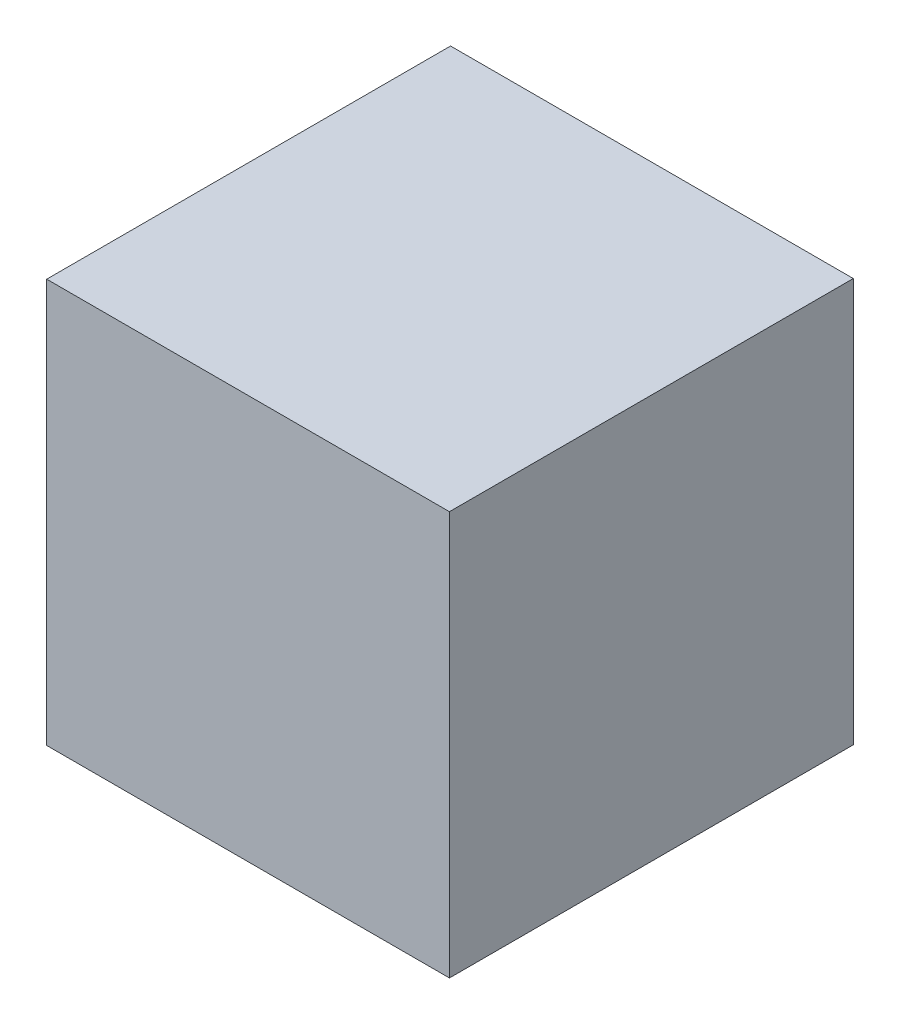
SolidWorks part; units mm, degrees
ref_plane "Front Plane" through (0, 0, 0) normal (0, 0, 1) x (1, 0, 0)
ref_plane "Top Plane" through (0, 0, 0) normal (0, 1, 0) x (1, 0, 0)
ref_plane "Right Plane" through (0, 0, 0) normal (1, 0, 0) x (0, 0, -1)
sketch "Sketch2" plane through (0, 0, 0) normal (0, 0, 1) x (1, 0, 0)
  line L1 (-457.2, 0) -> (457.2, 0)
  line L2 (-457.2, 0) -> (-457.2, 914.4)
  line L3 (-457.2, 914.4) -> (457.2, 914.4)
  line L4 (457.2, 0) -> (457.2, 914.4)
  dimension "D1" = 914.4
  dimension "D2" = 914.4
extrude "Boss-Extrude1" add sketch "Sketch2" along normal blind 914.4
shell "Shell2" thickness 2.54 removed face at (-457.2, 457.2, 457.2) outward yes
equation "\"W\"=36"
equation "\"D1@Sketch2\"=\"W\""
equation "\"H\"=36"
equation "\"D2@Sketch2\"=\"H\""
equation "\"L\"=36"
equation "\"D1@Boss-Extrude1\"=\"L\""
